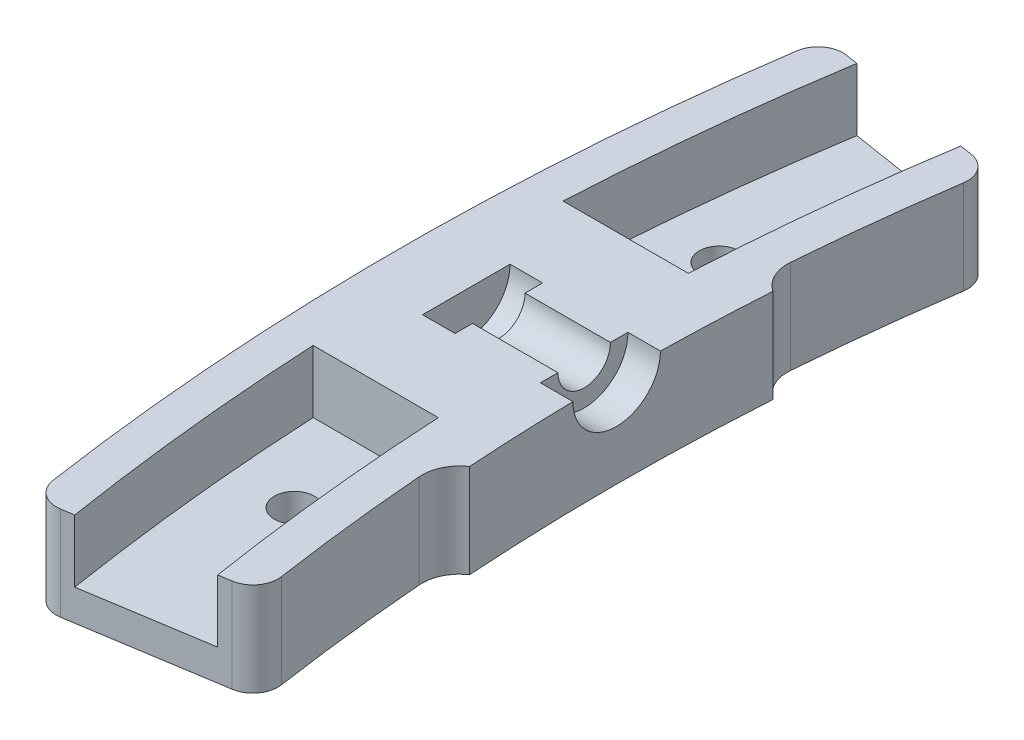
SolidWorks part; units mm, degrees
ref_plane "Front Plane" through (0, 0, 0) normal (0, 0, 1) x (1, 0, 0)
ref_plane "Top Plane" through (0, 0, 0) normal (0, 1, 0) x (1, 0, 0)
ref_plane "Right Plane" through (0, 0, 0) normal (1, 0, 0) x (0, 0, -1)
sketch "Sketch1" plane through (0, 0, 0) normal (0, 1, 0) x (1, 0, 0)
  line L0 (0, 0) -> (-197.5377, -31.2869) construction
  line L1 (0, 0) -> (-197.5377, 31.2869) construction
  line L2 (0, 0) -> (-195, 0) construction
  line L3 (-197.5377, 31.2869) -> (-187.6608, 29.7225)
  line L4 (-187.6608, -29.7225) -> (-197.5377, -31.2869)
  line L5 (0, 0) -> (-200.5007, -31.7562) construction
  line L6 (0, 0) -> (-200.5007, 31.7562) construction
  line L7 (-200.5007, 31.7562) -> (-184.6977, 29.2532)
  line L8 (-200.5007, -31.7562) -> (-184.6977, -29.2532)
  arc A0 (-197.5377, 31.2869) -> (-197.5377, -31.2869) centre (0, 0) ccw
  arc A1 (-187.6608, 29.7225) -> (-187.6608, -29.7225) centre (0, 0) ccw
  arc A2 (-192.5992, -30.5047) -> (-192.5992, 30.5047) centre (0, 0) cw construction
  arc A4 (-184.6977, 29.2532) -> (-184.6977, -29.2532) centre (0, 0) ccw
  arc A5 (-200.5007, 31.7562) -> (-200.5007, -31.7562) centre (0, 0) ccw
  dimension "D1" = 200
  dimension "D2" = 190
  dimension "D3" = 5
  dimension "D5" = 187
  dimension "D6" = 203
  dimension "D4" = 18
extrude "Boss-Extrude1" add sketch "Sketch1" along normal blind 10 contours A1 L3 A0 L4 | L7 A5 L8 A0 | A4 L7 A1 L8 region at (-200.6761, 0, 0) region at (-194.2416, 0, 0) region at (-187.7297, 0, 0)
ref_plane "Plane1" through (-195, 0, 0) normal (1, 0, 0) x (0, 0, -1)
sketch "Sketch15" plane through (0, 10, 0) normal (0, 1, 0) x (1, 0, 0)
  line L0 (-187.6608, -29.7225) -> (-197.5377, -31.2869) construction
  line L1 (-185, 10) -> (-205, 10)
  line L2 (-185, 10) -> (-185, -10)
  line L3 (-185, -10) -> (-205, -10)
  line L4 (-205, 10) -> (-205, -10)
  line L5 (-185, 10) -> (-205, -10) construction
  line L6 (-185, -10) -> (-205, 10) construction
  line L7 (-197.5377, 31.2869) -> (-187.6608, 29.7225) construction
  line L8 (-187.6608, -29.7225) -> (-197.5377, -31.2869)
  line L9 (-197.5377, 31.2869) -> (-187.6608, 29.7225)
  arc A2 (-187.6608, 29.7225) -> (-187.6608, -29.7225) centre (0, 0) ccw construction
  arc A3 (-197.5377, 31.2869) -> (-197.5377, -31.2869) centre (0, 0) ccw construction
  arc A4 (-187.6608, 29.7225) -> (-187.6608, -29.7225) centre (0, 0) ccw
  arc A5 (-197.5377, 31.2869) -> (-197.5377, -31.2869) centre (0, 0) ccw
  point P0 (-195, 0)
  line M5 (-200.5007, -31.7562) -> (-184.6977, -29.2532)
  line M7 (-184.6977, 29.2532) -> (-200.5007, 31.7562)
  dimension "D1" = 20
  dimension "D2" = 20
extrude "Cut-Extrude1" cut sketch "Sketch15" against normal blind 5 contours A5 L1 A4 M7 | L3 A5 A4 M5 region at (-193.9153, 10, -20.2762) region at (-193.9153, 10, 20.2762)
ref_plane "Plane2" through (-195, 0, 0) normal (-1, 0, 0) x (0, 0, 1)
sketch "Sketch12" plane through (0, 0, 0) normal (0, 1, 0) x (1, 0, 0)
  line L0 (0, 0) -> (-194.258, -16.9954) construction
  line L1 (0, 0) -> (-193.3317, -25.4526) construction
  line L2 (0, 0) -> (-195, 0) construction
  line L3 (0, 0) -> (-195, 0) construction
  line L4 (0, 0) -> (-194.258, 16.9954) construction
  line L5 (0, 0) -> (-193.3317, 25.4526) construction
  arc A0 (-192.5992, 30.5047) -> (-192.5992, -30.5047) centre (0, 0) ccw construction
  dimension "D1" = 10
  dimension "D2" = 15
hole_wizard "Ø3.2 (3.2) Diameter Hole1" positions "Sketch18" profile "Sketch17" hole size "Ø3.2" standard "ISO" end condition through all
sketch "Sketch18" plane through (0, 0, 0) normal (0, -1, 0) x (-1, 0, 0)
  point P3 (194.258, -16.9954)
  point P6 (194.258, 16.9954)
  point P13 (0, 0)
  point P14 (0, 0)
sketch "Sketch17" plane through (-194.258, 0, 16.9954) normal (1, 0, 0) x (0, 0, -1)
  line L0 (0, 0) -> (0, 10)
  line L1 (0, 10) -> (1.6, 10)
  line L2 (1.6, 10) -> (1.6, 0)
  line L5 (1.6, 0) -> (0, 0)
  line L11 (0, -6.35) -> (0, 107.95) construction
  dimension "Thru Hole Dia." = 3.2
  dimension "Thru Hole Depth" = 10
sketch "Sketch19" plane through (0, 0, 0) normal (0, 1, 0) x (1, 0, 0)
  line L0 (0, 0) -> (-185.1028, -12.1323) construction
  line L1 (0, 0) -> (-185.5, 0) construction
  line L2 (-185.1028, -12.1323) -> (-186.5996, -12.2304)
  line L3 (-185.1028, 12.1323) -> (-186.5996, 12.2304)
  arc A0 (-185.1028, 12.1323) -> (-185.1028, -12.1323) centre (0, 0) ccw
  arc A1 (-184.6977, 29.2532) -> (-184.6977, -29.2532) centre (0, 0) ccw construction
  arc A2 (-186.5996, 12.2304) -> (-186.5996, -12.2304) centre (0, 0) ccw
  dimension "D1" = 185.5
  dimension "D2" = 3.75
extrude "Boss-Extrude2" add sketch "Sketch19" along normal blind 10
fillet "Fillet1" radius 3 2 edges at (-186.5996, 5, -12.2304) (-186.5996, 5, 12.2304)
fillet "Fillet2" radius 2 4 edges at (-200.5007, 5, -31.7562) (-200.5007, 5, 31.7562) (-184.6977, 5, 29.2532) (-184.6977, 5, -29.2532)
sketch "Sketch20" plane through (0, 10, 0) normal (0, 1, 0) x (1, 0, 0)
  line L0 (0, 0) -> (-185, 0) construction
  line L1 (-185, 0) -> (-197.5, 0) construction
  dimension "D1" = 185
  dimension "D2" = 12.5
ref_plane "Plane3" through (-197.5, 0, 0) normal (1, 0, 0) x (0, 0, -1)
sketch "Sketch21" plane through (-197.5, 0, 0) normal (1, 0, 0) x (0, 0, -1)
  line L0 (12.1323, 10) -> (-12.1323, 10) construction
  circle A0 centre (0, 10) radius 2.1
  dimension "D1" = 4.2
extrude "Cut-Extrude2" cut sketch "Sketch21" along normal through all
sketch "Sketch22" plane through (-197.5, 0, 0) normal (1, 0, 0) x (0, 0, -1)
  line L0 (-2.1, 10) -> (2.1, 10) construction
  circle A0 centre (0, 10) radius 3.5
  dimension "D1" = 7
extrude "Cut-Extrude3" cut sketch "Sketch22" along normal blind 2.6
sketch "Sketch23" plane through (-197.5, 0, 0) normal (1, 0, 0) x (0, 0, -1)
  line L0 (-3.5, 10) -> (3.5, 10) construction
  circle A0 centre (0, 10) radius 2.5
  dimension "D1" = 5
extrude "Cut-Extrude4" [suppressed] cut sketch "Sketch23" against normal blind 0.2 and the other way blind 2.7
sketch "Sketch24" [suppressed] plane through (0, 10, 0) normal (0, 1, 0) x (1, 0, 0)
  line L0 (-185.5, 0) -> (-197.5, 0) construction
  line L2 (-197.5, -2.5) -> (-197.5, 2.5) construction
  line L3 (-188.067, 0) -> (-185.467, 0)
  line L4 (-188.067, 0) -> (-188.067, 3.5)
  line L5 (-188.067, 3.5) -> (-185.467, 3.5)
  line L6 (-185.467, 0) -> (-185.467, 3.5)
  arc A0 (-185.4881, 2.1) -> (-185.4881, -2.1) centre (0, 0) ccw construction
  arc A1 (-185.1028, 12.1323) -> (-185.4881, 2.1) centre (0, 0) ccw construction
  dimension "D1" = 2.6
  dimension "D2" = 7
revolve "Cut-Revolve1" [suppressed] cut sketch "Sketch24" angle 360 about L0
sketch "Sketch25" [suppressed] plane through (-188.067, 0, 0) normal (1, 0, 0) x (0, 0, -1)
  line L0 (-2.5, 10) -> (2.5, 10) construction
  circle A0 centre (0, 10) radius 2.5
  dimension "D1" = 5
extrude "Cut-Extrude5" [suppressed] cut sketch "Sketch25" against normal up to surface (9.633 mm away) up to face at (-197.5, 8.25, 0)
sketch "Sketch26" plane through (0, 0, 0) normal (0, -1, 0) x (1, 0, 0)
  line L2 (-198.5155, -31.4418) -> (-186.6626, -29.5645)
  line L3 (-186.6626, 29.5645) -> (-198.5155, 31.4418)
  line L4 (-198.5155, -31.4418) -> (-186.6626, -29.5645)
  line L5 (-186.6626, 29.5645) -> (-198.5155, 31.4418)
  arc A10 (-200.8068, 29.7596) -> (-200.8068, -29.7596) centre (0, 0) ccw
  arc A11 (-200.8068, -29.7596) -> (-198.5155, -31.4418) centre (-198.8284, -29.4664) ccw
  arc A12 (-186.6626, -29.5645) -> (-184.9969, -27.2971) centre (-186.9755, -27.5891) ccw
  arc A13 (-186.4092, -14.8532) -> (-184.9969, -27.2971) centre (0, 0) ccw
  arc A14 (-185.1028, -12.1323) -> (-186.4092, -14.8532) centre (-183.4187, -14.6149) ccw
  arc A15 (-185.1028, 12.1323) -> (-185.1028, -12.1323) centre (0, 0) ccw
  arc A16 (-186.4092, 14.8532) -> (-185.1028, 12.1323) centre (-183.4187, 14.6149) ccw
  arc A17 (-184.9969, 27.2971) -> (-186.4092, 14.8532) centre (0, 0) ccw
  arc A18 (-184.9969, 27.2971) -> (-186.6626, 29.5645) centre (-186.9755, 27.5891) ccw
  arc A19 (-198.5155, 31.4418) -> (-200.8068, 29.7596) centre (-198.8284, 29.4664) ccw
  arc A20 (-200.8068, 29.7596) -> (-200.8068, -29.7596) centre (0, 0) ccw
  arc A21 (-200.8068, -29.7596) -> (-198.5155, -31.4418) centre (-198.8284, -29.4664) ccw
  arc A22 (-186.6626, -29.5645) -> (-184.9969, -27.2971) centre (-186.9755, -27.5891) ccw
  arc A23 (-186.4092, -14.8532) -> (-184.9969, -27.2971) centre (0, 0) ccw
  arc A24 (-185.1028, -12.1323) -> (-186.4092, -14.8532) centre (-183.4187, -14.6149) ccw
  arc A25 (-185.1028, 12.1323) -> (-185.1028, -12.1323) centre (0, 0) ccw
  arc A26 (-186.4092, 14.8532) -> (-185.1028, 12.1323) centre (-183.4187, 14.6149) ccw
  arc A27 (-184.9969, 27.2971) -> (-186.4092, 14.8532) centre (0, 0) ccw
  arc A28 (-184.9969, 27.2971) -> (-186.6626, 29.5645) centre (-186.9755, 27.5891) ccw
  arc A29 (-198.5155, 31.4418) -> (-200.8068, 29.7596) centre (-198.8284, 29.4664) ccw
  dimension "D1" = 0
extrude "Cut-Extrude6" cut sketch "Sketch26" against normal blind 2.5
sketch "Sketch27" plane through (0, 10, 0) normal (0, 1, 0) x (1, 0, 0)
  line L0 (-197.5, 0) -> (-185.467, 0) construction
  line L1 (-197.5, -3.5) -> (-197.5, 3.5) construction
  line L3 (-188.067, 3.5) -> (-185.467, 3.5)
  line L4 (-188.067, 3.5) -> (-188.067, 0)
  line L5 (-188.067, 0) -> (-185.467, 0)
  line L6 (-185.467, 3.5) -> (-185.467, 0)
  arc A1 (-185.1028, 12.1323) -> (-185.4881, 2.1) centre (0, 0) ccw construction
  dimension "D1" = 2.6
  dimension "D2" = 7
revolve "Cut-Revolve3" cut sketch "Sketch27" angle 360 about L0
